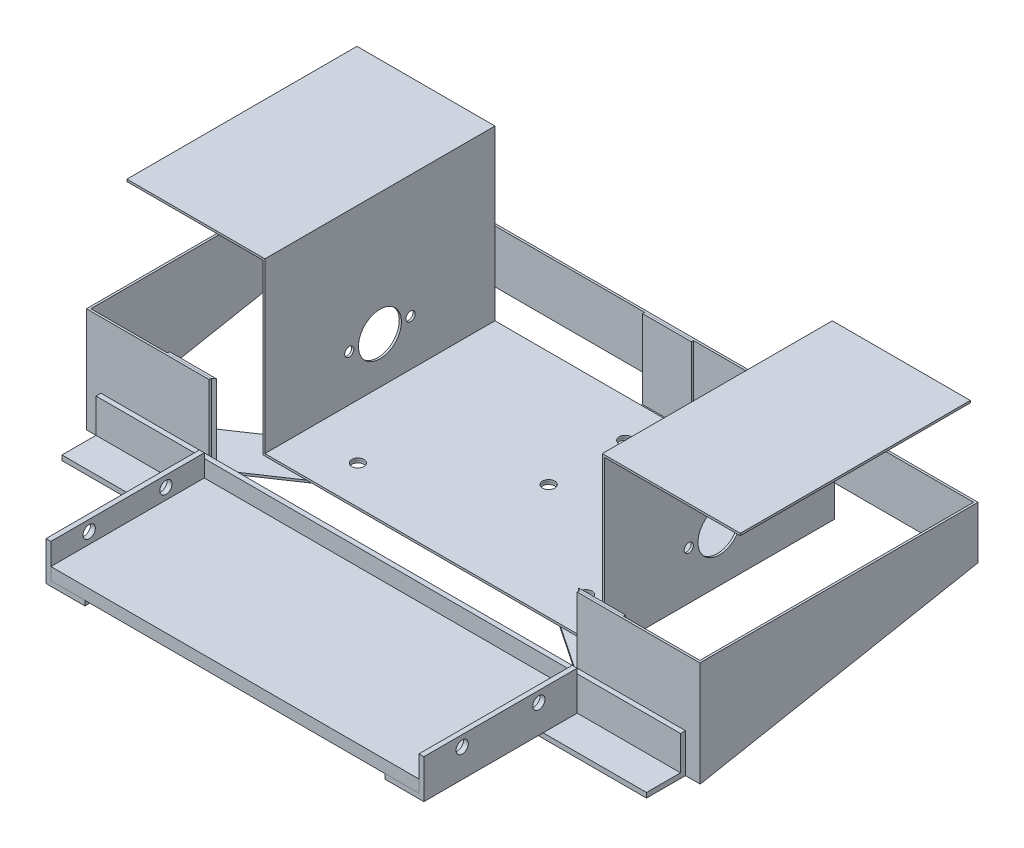
SolidWorks part; units mm, degrees
note: The reader was unsure of these and kept them because the rebuilt part matched: shared geometry of "Sketch27<3>".
ref_plane "Front Plane" through (0, 0, 0) normal (0, 0, 1) x (1, 0, 0)
ref_plane "Top Plane" through (0, 0, 0) normal (0, 1, 0) x (1, 0, 0)
ref_plane "Right Plane" through (0, 0, 0) normal (1, 0, 0) x (0, 0, -1)
sketch "Bounding Box" plane through (0, 0, 0) normal (0, 1, 0) x (1, 0, 0)
  line L0 (0, -54.1882) -> (0, 0) construction
  line L1 (100, -179.1882) -> (-100, -179.1882)
  line L2 (100, -179.1882) -> (100, 70.8118)
  line L3 (100, 70.8118) -> (-100, 70.8118)
  line L4 (-100, -179.1882) -> (-100, 70.8118)
  line L5 (100, -179.1882) -> (-100, 70.8118) construction
  line L6 (100, 70.8118) -> (-100, -179.1882) construction
  dimension "D1" = 250
  dimension "D2" = 200
sketch "Sketch2" plane through (0, 0, 0) normal (0, 1, 0) x (1, 0, 0)
  line L4 (0, 34.9582) -> (0, -179.1882) construction
  line L6 (100, -179.1882) -> (-100, -179.1882) construction
  line L8 (-66.6, 34.925) -> (-92, 34.925)
  line L9 (-66.6, 34.925) -> (-66.6, -34.925)
  line L10 (-66.6, -34.925) -> (-92, -34.925)
  line L11 (-92, 34.925) -> (-92, -34.925)
  line L12 (-66.6, 34.925) -> (-92, -34.925) construction
  line L13 (-66.6, -34.925) -> (-92, 34.925) construction
  line L19 (-100, -179.1882) -> (-100, 70.8118) construction
  line L20 (-55.7, 34.9582) -> (-55.7, -40.925)
  line L21 (-60, -52.2839) -> (-60, -102.2839)
  line L22 (-55.7, -40.925) -> (-55, -40.925)
  line L23 (-55, 34.9582) -> (-55, -40.925)
  line L24 (-55, -40.925) -> (-55, -42.925)
  line L25 (-55, -42.925) -> (-96, -42.925)
  line L26 (-96, 36.0781) -> (-96, -50.925)
  line L27 (-89.815, -52.2839) -> (89.815, -52.2839)
  line L28 (-89.815, -52.2839) -> (-89.815, -202.2839)
  line L29 (-89.815, -202.2839) -> (89.815, -202.2839)
  line L30 (89.815, -52.2839) -> (89.815, -202.2839)
  line L31 (-89.815, -52.2839) -> (89.815, -202.2839) construction
  line L32 (-89.815, -202.2839) -> (89.815, -52.2839) construction
  line L33 (-55, 13) -> (-10, 13)
  line L34 (-55, 13) -> (-55, -13)
  line L35 (-55, -13) -> (-10, -13)
  line L36 (-10, 13) -> (-10, -13)
  line L37 (-60, -102.2839) -> (60, -102.2839)
  line L38 (60, -102.2839) -> (60, -52.2839)
  line L41 (-96, -50.925) -> (-100, -50.925)
  line L43 (-96, 36.0781) -> (-100, 36.0781)
  line L44 (-100, 36.0781) -> (-100, -50.925)
  line L45 (-55.7, 0) -> (-10, 0) construction
  line L46 (-95.3, -50.925) -> (-95.3, -42.925)
  line L47 (-96, -50.925) -> (0, -50.925)
  line L48 (-55.7, 34.9582) -> (0, 34.9582)
  line L49 (0, 34.9582) -> (0, -50.925)
  point P0 (-79.3, 0)
  point P6 (-10, 0)
  point P15 (79.3, 0)
  point P27 (0, -127.2839)
  point P44 (0, -102.2839)
  dimension "D17" = 45
  dimension "D1" = 69.85
  dimension "D2" = 25.4
  dimension "D3" = 8
  dimension "D4" = 6
  dimension "D5" = 16
  dimension "D6" = 0.7
  dimension "D7" = 4
  dimension "D8" = 2
  dimension "D9" = 120
  dimension "D10" = 0.7
  dimension "D11" = 150
  dimension "D12" = 45
  dimension "D13" = 26
  dimension "D14" = 50
extrude "Platform" add sketch "Sketch2" against normal blind 4 from offset 18 separate body contours L37 L38 L27 L21
sketch "Sketch3" plane through (0, 0, 0) normal (1, 0, 0) x (0, 0, -1)
  line L0 (-52.2839, 23.5) -> (-52.2839, 12.4)
  line L1 (-52.2839, 12.4) -> (-63.3839, 12.4)
  line L2 (-63.3839, 12.4) -> (-63.3839, 10.8)
  line L3 (-63.3839, 10.8) -> (-50.6839, 10.8)
  line L4 (-50.6839, 10.8) -> (-50.6839, 23.5)
  line L5 (-50.6839, 23.5) -> (-52.2839, 23.5)
  line L7 (-52.2839, 14) -> (-52.2839, 18) construction
  line L8 (-102.2839, 14) -> (-52.2839, 14) construction
  dimension "D1" = 1.6
  dimension "D2" = 12.7
  dimension "D3" = 1.6
extrude "Alu Angle Platform Rest" add sketch "Sketch3" along normal mid plane 190.6 separate body
sketch "Drive Axle Holes" plane through (0, 0, 0) normal (1, 0, 0) x (0, 0, -1)
  line L0 (0, 0) -> (0, 35) construction
  line L1 (13, 0) -> (-13, 0) construction
  line L2 (10, 35) -> (-10, 35) construction
  circle A0 centre (0, 35) radius 7
  circle A1 centre (0, 35) radius 5
  point P4 (0, 0)
  point P8 (0, 35)
  dimension "D3" = 14
  dimension "D4" = 10
  dimension "D1" = 35
  dimension "D2" = 20
sketch "Sketch8" plane through (0, 0, 102.2839) normal (0, 0, 1) x (1, 0, 0)
  line L0 (-48.9, 12.4) -> (-61.6, 12.4)
  line L2 (-61.6, 12.4) -> (-61.6, 25.1)
  line L3 (-60, 14) -> (-60, 18) construction
  line L4 (-61.6, 25.1) -> (-60, 25.1)
  line L5 (-60, 25.1) -> (-60, 14)
  line L6 (-60, 14) -> (-48.9, 14)
  line L7 (-48.9, 14) -> (-48.9, 12.4)
  line L8 (-60, 14) -> (60, 14) construction
  dimension "D1" = 12.7
  dimension "D2" = 1.6
extrude "Platform Angle RH" add sketch "Sketch8" against normal up to surface (50 mm away) separate body up to face at (0, 17.95, 52.2839)
sketch "Sketch19" plane through (0, 0, 0) normal (1, 0, 0) x (0, 0, -1)
  line L0 (-102.2839, 21.6) -> (-52.2839, 21.6) construction
  line L4 (-102.2839, 14) -> (-102.2839, 25.1) construction
  line L5 (-52.2839, 14) -> (-52.2839, 25.1) construction
  line L6 (-52.2839, 25.1) -> (-102.2839, 25.1) construction
  circle A0 centre (-89.7839, 21.6) radius 2
  circle A1 centre (-64.7839, 21.6) radius 2
  point P12 (-80.6179, 21.6)
  point P13 (0, 0)
  point P16 (0, 0)
  dimension "D2" = 4
  dimension "D1" = 3.5
  dimension "D3" = 12.5
  dimension "D4" = 12.5
extrude "Cut-Extrude2" cut sketch "Sketch19" against normal up to next from surface
mirror "Platform Angle LH" about plane through (0, 0, 0) normal (1, 0, 0) of bodies 136 110
sketch "Sketch20" plane through (0, 0, 0) normal (0, 1, 0) x (1, 0, 0)
  line L0 (-60, -50.6839) -> (-100, -50.6839)
  line L1 (-100, -50.6839) -> (-100, 40)
  line L2 (-100, 40) -> (0, 40)
  line L3 (0, 213.0393) -> (0, -213.0393) construction
  line L7 (-200055.7, 0) -> (199990, 0) construction
  line L8 (95.3, -50.6839) -> (-95.3, -50.6839) construction
  point P5 (0, 39.0461)
  point P8 (0, 0)
  point P11 (-61.5437, -47.6421)
  dimension "D1" = 100
  dimension "D2" = 40
  dimension "D3" = 40
ref_plane "Plane1" through (0, 35, 0) normal (0, 1, 0) x (1, 0, 0)
extrude "Outer Frame" add sketch "Sketch20" along normal blind 10 and the other way up to surface from surface separate body thin
sketch "Sketch22" plane through (0, 0, 0) normal (1, 0, 0) x (0, 0, -1)
  line L0 (40, 27.9) -> (-49.9839, 10.8)
  line L1 (40, 10.8) -> (40, 45) construction
extrude "Cut-Extrude-Thin1" cut sketch "Sketch22" against normal up to surface (100 mm away) thin up to face at (-100, 27.9, 5.342) thin type one direction reverse wall 0.7
mirror "Mirror1" about plane through (0, 0, 0) normal (1, 0, 0) of bodies 139
sketch "Sketch24" plane through (0, 0, 0) normal (0, 0, 1) x (1, 0, 0)
  line L0 (-100, 75) -> (-55, 75)
  line L1 (-55, 75) -> (-55, 20)
  line L2 (-55, 20) -> (55, 20)
  line L3 (55, 20) -> (55, 75)
  line L4 (55, 75) -> (100, 75)
  line L5 (-89.815, 0) -> (89.815, 0) construction
  point P6 (0, 20)
  point P11 (-54.9895, 20)
  point P13 (0, 0)
  point P15 (0, 0)
  dimension "D1" = 15
  dimension "D2" = 75
extrude "Extrude-Thin3" add sketch "Sketch24" against normal mid plane 75 separate body thin contours L0 L1 L2 L3 L4
extrude "Cut-Extrude3" cut sketch "Drive Axle Holes" against normal through all both and the other way through all contours A1 | A0 A1
hole_wizard "Ø3.0mm Dowel Hole1" positions "Sketch25" profile "Sketch26" hole size "Ø3.0" standard "ANSI Metric" end condition through all
sketch "Sketch25" plane through (55.7, 0, 0) normal (1, 0, 0) x (0, 0, -1)
  point P0 (-10, 35)
  point P3 (10, 35)
sketch "Sketch26" plane through (55.7, 35, 10) normal (0, 1, 0) x (0, 0, -1)
  line L0 (0, 0) -> (0, 155.7)
  line L1 (0, 155.7) -> (1.5, 155.7)
  line L2 (1.5, 155.7) -> (1.5, 0)
  line L5 (1.5, 0) -> (0, 0)
  line L11 (0, -6.35) -> (0, 107.95) construction
  dimension "Thru Hole Dia." = 3
  dimension "Thru Hole Depth" = 155.7
sketch "Sketch27" plane through (0, 19.3, 0) normal (0, -1, 0) x (-1, 0, 0)
  line L0 (74.3373, -40.3437) -> (8, 4.2611)
  line L3 (8, 4.2611) -> (8, 39.3)
  line L6 (99.3, 39.3) -> (-99.3, 39.3) construction
  line L7 (8, 39.3) -> (-8, 39.3)
  line L8 (-8, 39.3) -> (-8, 4.2611)
  line L9 (-8, 4.2611) -> (-74.3373, -40.3437)
  line L10 (-74.3373, -40.3437) -> (-74.3373, -49.9839)
  line L11 (-60, -49.9839) -> (-99.3, -49.9839) construction
  line L12 (-74.3373, -49.9839) -> (-60, -49.9839)
  line L13 (-60, -49.9839) -> (0, -9.6403)
  line L14 (0, 34.9582) -> (0, -50.925) construction
  line L15 (0, -9.6403) -> (60, -49.9839)
  line L16 (60, -49.9839) -> (74.3373, -49.9839)
  line L17 (60, -49.9839) -> (99.3, -49.9839) construction
  line L18 (74.3373, -49.9839) -> (74.3373, -40.3437)
  line L19 (0, 39.3) -> (0, -34.3097) construction
  line L20 (0, 0) -> (74.3373, -49.9839) construction
  line L21 (0, 0) -> (-74.3373, -49.9839) construction
  line L22 (8, 4.2611) -> (-8, 4.2611) construction
  line L23 (41.6325, -18.3532) -> (32.7047, -31.6308) construction
  line L24 (-32.7047, -31.6308) -> (-41.6325, -18.3532) construction
  line L25 (-74.3373, -49.2839) -> (-58.9589, -49.2839)
  line L26 (-8, 38.6) -> (8, 38.6)
  line L27 (74.3373, -49.2839) -> (58.9589, -49.2839)
  point P22 (0, 39.3)
  point P30 (-37.1686, -24.992)
  point P31 (37.1686, -24.992)
  line M23 (-55.7, -37.5) -> (55.7, -37.5)
  line M24 (55.7, -37.5) -> (55.7, 37.5)
  line M25 (55.7, 37.5) -> (-55.7, 37.5)
  line M26 (-55.7, 37.5) -> (-55.7, -37.5)
  dimension "D1" = 16
  dimension "D2" = 0.7
  dimension "D3" = 0.7
extrude "Boss-Extrude1" add sketch "Sketch27" along normal blind 0.7 separate body contours L8 L26 L3 L7 | L26 L8 L3 M25 | L13 L15 L0 L3 L8 L9 M23 M24 M25 M26 | L27 L18 L0 L15 M24 M23 | L18 L27 L15 L16 | L10 L25 L13 L9 M23 M26 | L25 L10 L12 L13
extrude "Boss-Extrude2" add sketch "Sketch27<3>" against normal up to surface (25.7 mm away) separate body contours L8 L26 L3 L7 | L25 L10 L12 L13 | L18 L27 L15 L16
sketch "Sketch27<3>" plane through (0, 19.3, 0) normal (0, -1, 0) x (-1, 0, 0) same geometry as "Sketch27"
sketch "Sketch28" plane through (0, 20, 0) normal (0, 1, 0) x (1, 0, 0)
  line L0 (0, 0) -> (-74.3373, -49.9839) construction
  line L1 (0, 0) -> (74.3373, -49.9839) construction
  line L2 (-37.1806, -25) -> (37.1806, -25) construction
  line L3 (0, 200039.3) -> (0, -200034.3097) construction
  circle A0 centre (0, 0) radius 2
  circle A1 centre (0, 25) radius 2
  circle A2 centre (-37.1806, -25) radius 2
  circle A3 centre (37.1806, -25) radius 2
  point P9 (0, 0)
  dimension "D3" = 4
  dimension "D1" = 25
  dimension "D2" = 25
extrude "Cut-Extrude4" cut sketch "Sketch28" along normal through all and the other way through all
